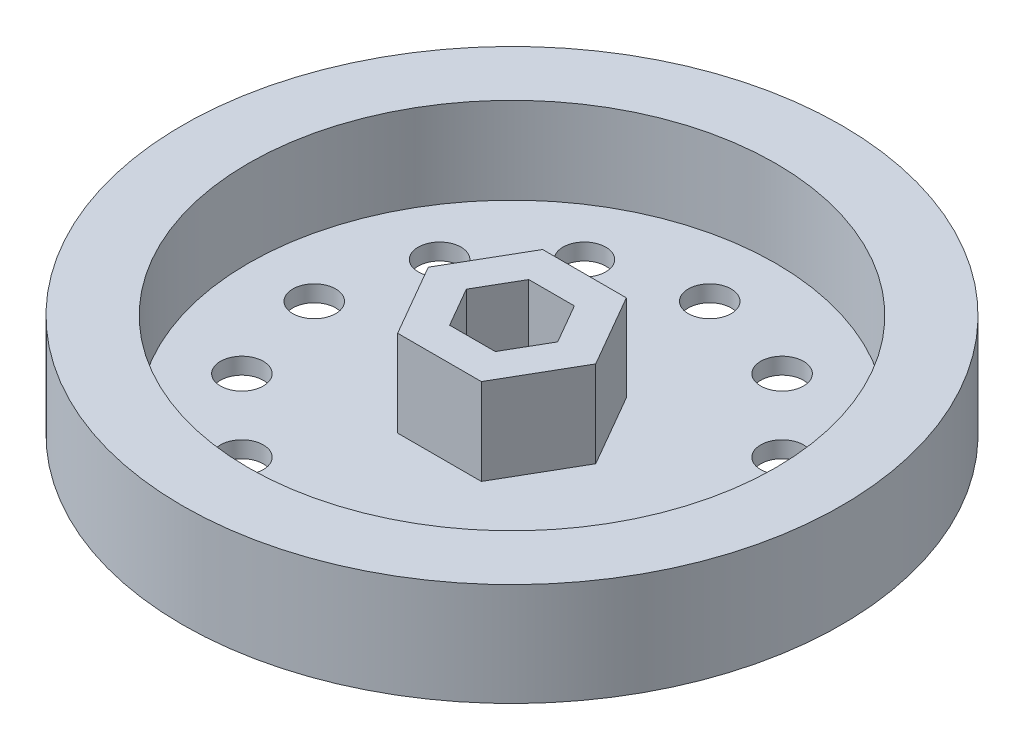
SolidWorks part; units mm, degrees
ref_plane "Front Plane" through (0, 0, 0) normal (0, 0, 1) x (1, 0, 0)
ref_plane "Top Plane" through (0, 0, 0) normal (0, 1, 0) x (1, 0, 0)
ref_plane "Right Plane" through (0, 0, 0) normal (1, 0, 0) x (0, 0, -1)
sketch "Sketch1" plane through (0, 0, 0) normal (0, 1, 0) x (1, 0, 0)
  circle A0 centre (0, 0) radius 50.8
  dimension "D1" = 101.6
extrude "Boss-Extrude1" add sketch "Sketch1" along normal blind 15.875
sketch "Sketch4" plane through (0, 15.875, 0) normal (0, 1, 0) x (1, 0, 0)
  line L0 (-3.5195, 6.096) -> (3.5195, 6.096)
  line L1 (3.5195, 6.096) -> (7.0391, 0)
  line L2 (7.0391, 0) -> (3.5195, -6.096)
  line L3 (3.5195, -6.096) -> (-3.5195, -6.096)
  line L4 (-3.5195, -6.096) -> (-7.0391, 0)
  line L5 (-7.0391, 0) -> (-3.5195, 6.096)
  point P7 (0, 6.096)
  dimension "D1" = 120
  dimension "D2" = 12.192
extrude "Hex hole" cut sketch "Sketch4" against normal blind 13.97 contours L5 L0 L1 L2 L3 L4
sketch "Sketch5" plane through (0, 1.905, 0) normal (0, 1, 0) x (1, 0, 0)
  circle A0 centre (0, 0) radius 4.191
  dimension "D1" = 8.382
extrude "Centerhole" cut sketch "Sketch5" against normal through all contours A0
sketch "Sketch6" plane through (0, 15.875, 0) normal (0, 1, 0) x (1, 0, 0)
  line L27 (12.9049, 0) -> (6.4525, 11.176)
  line L28 (6.4525, -11.176) -> (12.9049, 0)
  line L29 (-6.4525, -11.176) -> (6.4525, -11.176)
  line L30 (-12.9049, 0) -> (-6.4525, -11.176)
  line L31 (-6.4525, 11.176) -> (-12.9049, 0)
  line L32 (6.4525, 11.176) -> (-6.4525, 11.176)
  line L33 (12.9049, 0) -> (6.4525, 11.176)
  line L34 (6.4525, -11.176) -> (12.9049, 0)
  line L35 (-6.4525, -11.176) -> (6.4525, -11.176)
  line L36 (-12.9049, 0) -> (-6.4525, -11.176)
  line L37 (-6.4525, 11.176) -> (-12.9049, 0)
  line L38 (6.4525, 11.176) -> (-6.4525, 11.176)
  circle A2 centre (0, 0) radius 40.64
  circle A3 centre (0, 0) radius 40.64
  dimension "D1" = 10.16
  dimension "D2" = 5.08
extrude "Cut-Extrude1" cut sketch "Sketch6" against normal offset from surface (13.335 mm away) 2.54 up to face at (0, 0, 4.191)
sketch "Sketch7" plane through (0, 0, 0) normal (0, -1, 0) x (1, 0, 0)
  circle A0 centre (0, 30.48) radius 3.302
  circle A1 centre (15.24, 26.3965) radius 3.302
  circle A2 centre (26.3965, 15.24) radius 3.302
  circle A3 centre (30.48, 0) radius 3.302
  circle A4 centre (26.3965, -15.24) radius 3.302
  circle A5 centre (15.24, -26.3965) radius 3.302
  circle A6 centre (0, -30.48) radius 3.302
  circle A7 centre (-15.24, -26.3965) radius 3.302
  circle A8 centre (-26.3965, -15.24) radius 3.302
  circle A9 centre (-30.48, 0) radius 3.302
  circle A10 centre (-26.3965, 15.24) radius 3.302
  circle A11 centre (-15.24, 26.3965) radius 3.302
  point P4 (-25.0127, 38.0038)
  point P5 (0, 0)
  point P27 (0, 0)
  point P28 (0, 0)
  dimension "D1" = 6.604
  dimension "D2" = 30.48
extrude "Cut-Extrude2" cut sketch "Sketch7" against normal through all
